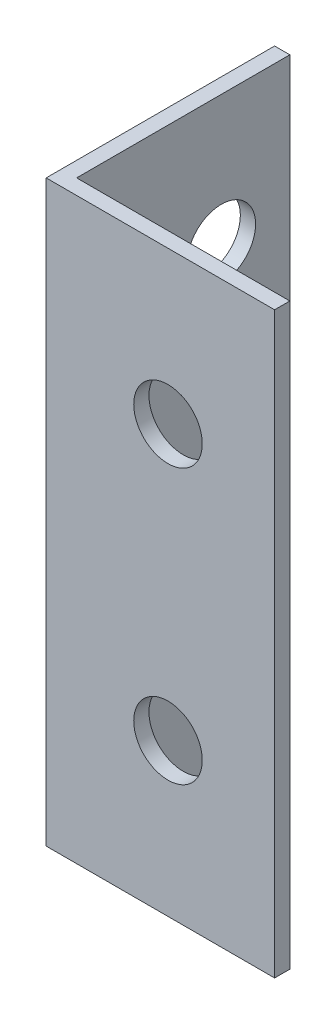
SolidWorks part; units mm, degrees
material "1060 Сплав"
ref_plane "Спереди" through (0, 0, 0) normal (0, 0, 1) x (1, 0, 0)
ref_plane "Сверху" through (0, 0, 0) normal (0, 1, 0) x (1, 0, 0)
ref_plane "Справа" through (0, 0, 0) normal (1, 0, 0) x (0, 0, -1)
sketch "Эскиз1" plane through (0, 0, 0) normal (0, 1, 0) x (1, 0, 0)
  line L0 (0, 0) -> (0, 15)
  line L1 (0, 15) -> (1, 15)
  line L2 (1, 15) -> (1, 1)
  line L3 (1, 1) -> (15, 1)
  line L4 (15, 1) -> (15, 0)
  line L5 (15, 0) -> (0, 0)
  dimension "D1" = 1
  dimension "D2" = 15
extrude "Бобышка-Вытянуть1" add sketch "Эскиз1" along normal blind 38
sketch "Эскиз2" plane through (1, 0, 0) normal (1, 0, 0) x (0, 0, -1)
  circle A0 centre (10.5, 29.5) radius 2.25 construction
  circle A1 centre (10.5, 29.5) radius 2.25
extrude "Вырез-Вытянуть1" cut sketch "Эскиз2" against normal through all
sketch "Эскиз3" plane through (0, 0, -1) normal (0, 0, -1) x (-1, 0, 0)
  line L0 (-8, 0) -> (-8, 10) construction
  line L1 (-15, 0) -> (-1, 0) construction
  circle A0 centre (-8, 10) radius 2.25
  dimension "D2" = 4.5
  dimension "D1" = 10
extrude "Вырез-Вытянуть2" cut sketch "Эскиз3" against normal through all
sketch "Эскиз4" plane through (0, 0, -1) normal (0, 0, -1) x (-1, 0, 0)
  line L0 (-8, 38) -> (-8, 28) construction
  line L1 (-15, 38) -> (-1, 38) construction
  circle A0 centre (-8, 28) radius 2.25
  dimension "D2" = 4.5
  dimension "D1" = 10
extrude "Вырез-Вытянуть3" cut sketch "Эскиз4" against normal through all
sketch "Эскиз5" plane through (0, 0, 0) normal (0, 0, 1) x (1, 0, 0)
  line L0 (7.5, 0) -> (7.5, 38) construction
  line L1 (0, 0) -> (15, 0) construction
  line L2 (0, 38) -> (15, 38) construction
